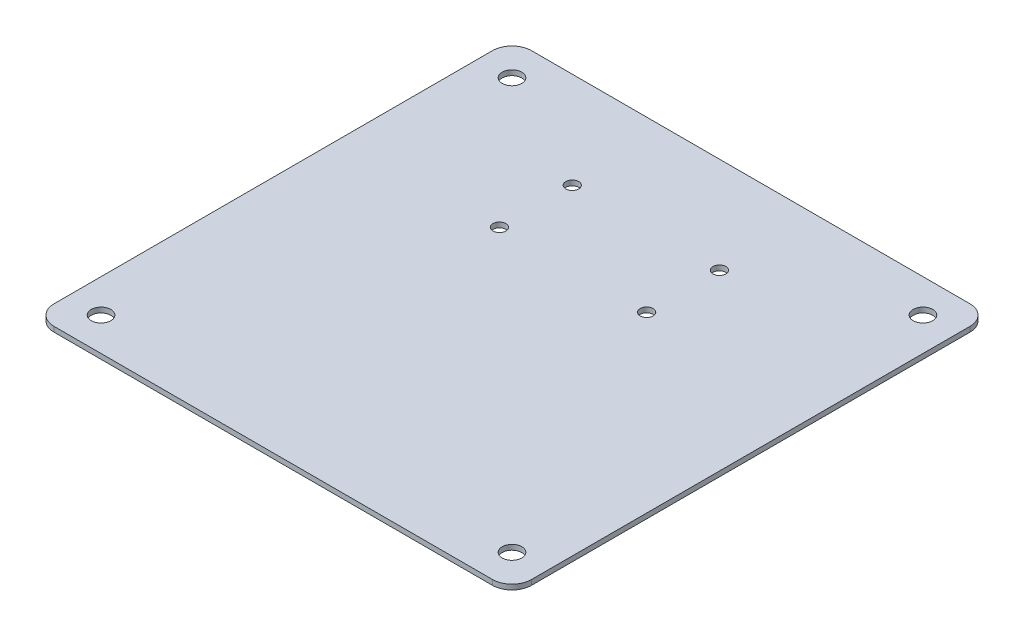
SolidWorks part; units mm, degrees
note: The reader was unsure of these and kept them because the rebuilt part matched: thickness of "Base-Flange1", "Sheet-Metal1", "Sheet-Metal2", "Sheet-Metal3".
material "AISI 1045 Steel, cold drawn"
ref_plane "Front Plane" through (0, 0, 0) normal (0, 0, 1) x (1, 0, 0)
ref_plane "Top Plane" through (0, 0, 0) normal (0, 1, 0) x (1, 0, 0)
ref_plane "Right Plane" through (0, 0, 0) normal (1, 0, 0) x (0, 0, -1)
sketch "Sketch1" plane through (0, 0, 0) normal (0, 1, 0) x (1, 0, 0)
  line L1 (-61, 61) -> (61, 61)
  line L2 (-61, 61) -> (-61, -61)
  line L3 (-61, -61) -> (61, -61)
  line L4 (61, 61) -> (61, -61)
  line L5 (-61, 61) -> (61, -61) construction
  line L6 (-61, -61) -> (61, 61) construction
  point P0 (0, 0)
  dimension "D1" = 122
base flange "Base-Flange1" sketch "Sketch1" thickness 1.3 reverse thickness direction no parameters "D1"=1.016
fillet "Fillet1" radius 5 4 edges at (61, -0.65, -61) (-61, -0.65, -61) (-61, -0.65, 61) (61, -0.65, 61)
sketch "Sketch3" plane through (0, 0, 0) normal (0, 1, 0) x (1, 0, 0)
  line L1 (-52.5, 52.5) -> (52.5, 52.5) construction
  line L2 (-52.5, 52.5) -> (-52.5, -52.5) construction
  line L3 (-52.5, -52.5) -> (52.5, -52.5) construction
  line L4 (52.5, 52.5) -> (52.5, -52.5) construction
  line L5 (-52.5, 52.5) -> (52.5, -52.5) construction
  line L6 (-52.5, -52.5) -> (52.5, 52.5) construction
  circle A0 centre (52.5, 52.5) radius 2.5
  circle A1 centre (-52.5, 52.5) radius 2.5
  circle A2 centre (-52.5, -52.5) radius 2.5
  circle A3 centre (52.5, -52.5) radius 2.5
  point P0 (0, 0)
  dimension "D2" = 5
  dimension "D1" = 105
extrude "Cut-Extrude1" cut sketch "Sketch3" against normal blind 10 normal cut yes
sketch "Sketch4" plane through (0, -1.3, 0) normal (0, -1, 0) x (-1, 0, 0)
  circle A0 centre (21.0238, 36.4225) radius 1.65
  circle A1 centre (21.0238, 17.8225) radius 1.65
  circle A2 centre (-16.5762, 17.8225) radius 1.65
  circle A3 centre (-16.5762, 36.4225) radius 1.65
  dimension "D1" = 3.3
extrude "Cut-Extrude2" cut sketch "Sketch4" against normal blind 10 normal cut yes
sketch "Bend-Lines1" [suppressed] plane through (0, 0, 0) normal (0, 1, 0) x (1, 0, 0)
sketch "Bounding-Box1" [suppressed] plane through (0, 0, 0) normal (0, 1, 0) x (1, 0, 0)
sheet metal parameters "Sheet-Metal1" thickness 1.3 parameters "D1"=1.016, "D7"=1.52
flat pattern "Flat-Pattern1" [suppressed]
sketch "Bend-Lines2" plane through (0, 0, 0) normal (0, 1, 0) x (1, 0, 0)
sketch3d "Bounding-Box2" [suppressed]
  line L0 (-60, -60, 0) -> (60, -60, 0) construction
  line L1 (-60, 60, 0) -> (60, 60, 0) construction
  line L2 (-60, -60, 0) -> (-60, 60, 0) construction
  line L3 (60, -60, 0) -> (60, 60, 0) construction
sheet metal parameters "Sheet-Metal2" thickness 1.3 parameters "D1"=1.016, "D7"=1.52
flat pattern "Flat-Pattern1"
sketch "Bend-Lines2" plane through (0, 0, 0) normal (0, 1, 0) x (1, 0, 0)
sketch3d "Bounding-Box2" [suppressed]
  line L0 (-60, -60, 0) -> (60, -60, 0) construction
  line L1 (-60, 60, 0) -> (60, 60, 0) construction
  line L2 (-60, -60, 0) -> (-60, 60, 0) construction
  line L3 (60, -60, 0) -> (60, 60, 0) construction
sheet metal parameters "Sheet-Metal3" thickness 1.3 parameters "D1"=1.016, "D7"=1.52
flat pattern "Flat-Pattern1"
sketch "Bend-Lines2" plane through (0, 0, 0) normal (0, 1, 0) x (1, 0, 0)
sketch3d "Bounding-Box2" [suppressed]
  line L0 (-60, -60, 0) -> (60, -60, 0) construction
  line L1 (-60, 60, 0) -> (60, 60, 0) construction
  line L2 (-60, -60, 0) -> (-60, 60, 0) construction
  line L3 (60, -60, 0) -> (60, 60, 0) construction
